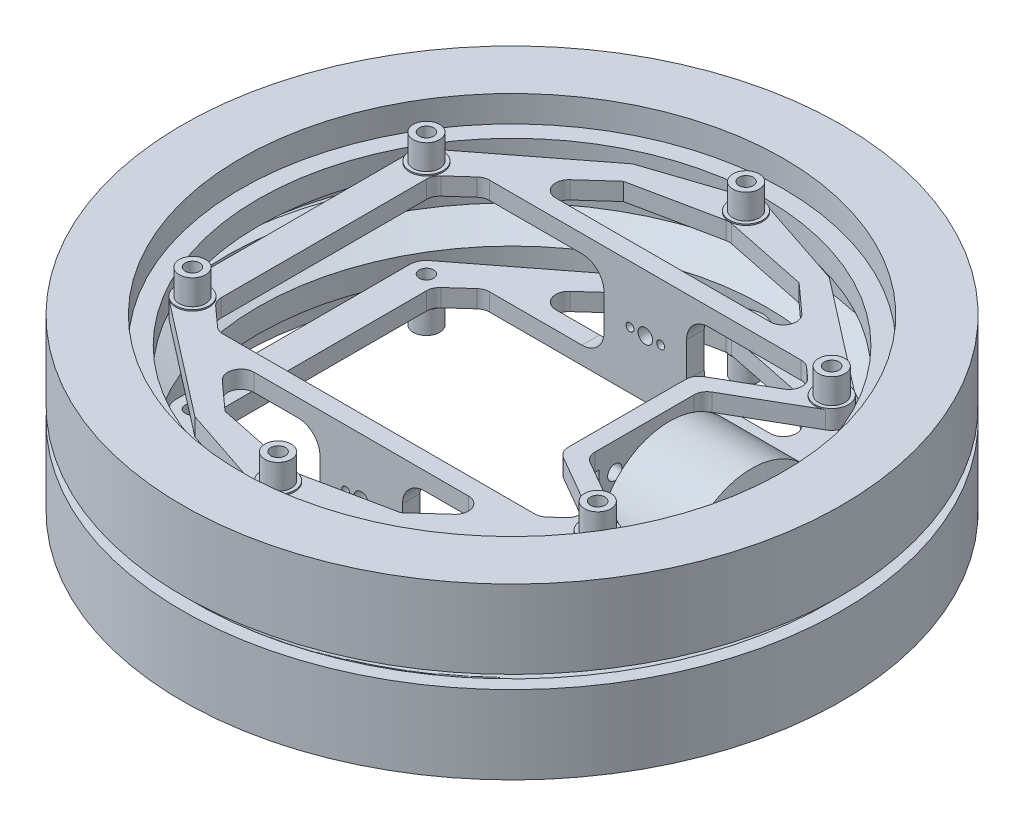
SolidWorks part; units mm, degrees
material "ABS"
ref_plane "Front Plane" through (0, 0, 0) normal (0, 0, 1) x (1, 0, 0)
ref_plane "Top Plane" through (0, 0, 0) normal (0, 1, 0) x (1, 0, 0)
ref_plane "Right Plane" through (0, 0, 0) normal (1, 0, 0) x (0, 0, -1)
other "Center of Mass"
ref_axis "Axis1" through (0, -45.4923, 0) along (0, 1, 0)
sketch "Sketch3" plane through (0, 0, 0) normal (0, 0, 1) x (1, 0, 0)
  line L0 (65, 1.5) -> (75, 1.5)
  line L1 (75, 1.5) -> (75, 19.3)
  line L2 (75, 19.3) -> (61.7495, 19.3)
  line L3 (0, 0) -> (85.6752, 0) construction
  line L4 (52.3451, 13.8) -> (57.3812, 3)
  line L5 (65, 1.5) -> (65, 4.5601)
  line L14 (35.8451, 16.3) -> (35.8451, 13.8)
  line L15 (35.8451, 13.8) -> (52.3451, 13.8)
  line L17 (54.4894, 16.3) -> (35.8451, 16.3)
  line L22 (0, -45.4923) -> (0, 86.3395) construction
  line L23 (57.3812, 3) -> (64.5, 3)
  line L24 (64.5, 3) -> (64.5, 7)
  line L25 (64.5, 7) -> (57.2495, 10.3809)
  line L26 (57.2495, 10.3809) -> (54.4894, 16.3)
  line L27 (65, 4.5601) -> (57.7495, 7.941)
  line L28 (57.7495, 7.941) -> (57.7495, 13.3)
  line L29 (57.7495, 13.3) -> (61.7495, 13.3)
  line L30 (61.7495, 13.3) -> (61.7495, 19.3)
  line L31 (53.2495, 19.3) -> (53.2495, 13.3) construction
  line L32 (44.7495, 19.3) -> (61.7495, 19.3) construction
  line L33 (44.7495, 19.3) -> (44.7495, 13.3) construction
  line L34 (44.7495, 13.3) -> (61.7495, 13.3) construction
  line L35 (61.7495, 19.3) -> (61.7495, 13.3) construction
  line L36 (50.2495, 19.3) -> (50.2495, 13.3) construction
  line L37 (56.2495, 19.3) -> (56.2495, 13.3) construction
  line L38 (75, -1.5) -> (75, -19.3)
  line L39 (65, -1.5) -> (75, -1.5)
  line L40 (65, -1.5) -> (65, -4.5601)
  line L41 (65, -4.5601) -> (57.7495, -7.941)
  line L42 (57.7495, -7.941) -> (57.7495, -13.3)
  line L43 (57.7495, -13.3) -> (61.7495, -13.3)
  line L44 (61.7495, -13.3) -> (61.7495, -19.3)
  line L45 (75, -19.3) -> (61.7495, -19.3)
  circle A0 centre (70, 0) radius 2.5
  point P32 (64.4892, 1.5)
  point P33 (56.9831, 0)
  point P34 (70, 1.5)
  point P35 (34.6232, 13.9)
  point P36 (49, 3.5657)
  point P45 (75.8697, 16.9)
  point P46 (75, 5.8131)
  dimension "D6" = 3
  dimension "D7" = 5
  dimension "D3" = 0.5
  dimension "D4" = 115
  dimension "D5" = 3
  dimension "D8" = 17
  dimension "D9" = 4
  dimension "D10" = 2.5
  dimension "D11" = 65
  dimension "D12" = 25
  dimension "D13" = 6
  dimension "D16" = 10
  dimension "D17" = 8
  dimension "D18" = 27.6
  dimension "D19" = 16.5
  dimension "D20" = 3
  dimension "D21" = 7
  dimension "D22" = 3
  dimension "D23" = 0.5
  dimension "D24" = 75
  dimension "D25" = 2
  dimension "D14" = 3
  dimension "D15" = 3
revolve "Revolve1" add sketch "Sketch3" angle 360 about axis through (0, -45.4923, 0) along (0, 1, 0) region at (68.168, 11.0369, 0) region at (67.7412, -10.8207, 0) region at (61.1248, 7.4705, 0)
revolve "Revolve2" add sketch "Sketch3<3>" angle 360 about L3 region at (61.1248, 7.4705, 0) region at (64.1841, 3.8966, 0)
sketch "Sketch3<3>" plane through (0, 0, 0) normal (0, 0, 1) x (1, 0, 0) same geometry as "Sketch3"
sketch "Sketch4" plane through (0, 0, 0) normal (0, 1, 0) x (1, 0, 0)
  line L0 (0, 0) -> (0, 53.2495) construction
  line L1 (0, 0) -> (46.1155, 26.6248) construction
  line L2 (0, 0) -> (46.1155, -26.6248) construction
  line L3 (0, 0) -> (0, -53.2495) construction
  line L4 (0, 0) -> (-46.1155, -26.6248) construction
  line L5 (0, 0) -> (-46.1155, 26.6248) construction
  line L6 (-1.2011, 56.8547) -> (-22.3876, 49.7965)
  line L7 (-48.4414, 29.6297) -> (-22.3876, 49.7965)
  line L8 (-49.9155, 26.6248) -> (-49.9155, -26.6248)
  line L9 (48.4414, 29.6297) -> (22.3876, 49.7965)
  line L10 (1.2011, 56.8547) -> (22.3876, 49.7965)
  line L11 (0, 0) -> (130.3481, 0) construction
  line L12 (48.0155, 23.3339) -> (30.1301, 13.0077)
  line L13 (30.1301, 13.0077) -> (30.1301, -13.0077)
  line L14 (48.0155, -23.3339) -> (30.1301, -13.0077)
  line L15 (35.8451, 13.8) -> (35.8451, -13.8) construction
  line L16 (48.4414, -29.6297) -> (22.3876, -49.7965)
  line L17 (-20, 45.3218) -> (20, 45.3218) construction
  line L18 (-20, 45.3218) -> (-20, 35.3218) construction
  line L19 (-20, 35.3218) -> (20, 35.3218) construction
  line L20 (20, 45.3218) -> (20, 35.3218) construction
  line L21 (1.2011, -56.8547) -> (22.3876, -49.7965)
  line L22 (-1.2011, -56.8547) -> (-22.3876, -49.7965)
  line L23 (-48.4414, -29.6297) -> (-22.3876, -49.7965)
  line L24 (-20, 45.3218) -> (-42.8246, 24.7248)
  line L25 (-20, 45.3218) -> (0, 49.4495)
  line L26 (0, 49.4495) -> (20, 45.3218)
  line L27 (20, 45.3218) -> (42.8246, 24.7248)
  line L28 (-32.1896, 34.3218) -> (32.1896, 34.3218)
  line L29 (-36.6222, 30.3218) -> (36.6222, 30.3218)
  line L30 (-42.8246, 24.7248) -> (-42.8246, -24.7248)
  line L31 (26.1301, -15.0862) -> (26.1301, 15.0862)
  line L32 (26.1301, 15.0862) -> (42.8246, 24.7248)
  line L33 (-32.1896, -34.3218) -> (32.1896, -34.3218)
  line L34 (-36.6222, -30.3218) -> (36.6222, -30.3218)
  line L35 (-20, -45.3218) -> (-42.8246, -24.7248)
  line L36 (0, -49.4495) -> (20, -45.3218)
  line L37 (-20, -45.3218) -> (0, -49.4495)
  line L38 (20, -45.3218) -> (42.8246, -24.7248)
  line L39 (26.1301, -15.0862) -> (42.8246, -24.7248)
  circle A1 centre (0, 53.2495) radius 3
  circle A3 centre (0, 53.2495) radius 3.8
  circle A4 centre (0, 53.2495) radius 1.65
  circle A5 centre (46.1155, 26.6248) radius 1.65
  circle A6 centre (46.1155, 26.6248) radius 3
  circle A7 centre (46.1155, 26.6248) radius 3.8
  circle A8 centre (46.1155, -26.6248) radius 1.65
  circle A9 centre (46.1155, -26.6248) radius 3
  circle A10 centre (46.1155, -26.6248) radius 3.8
  circle A11 centre (0, -53.2495) radius 1.65
  circle A12 centre (0, -53.2495) radius 3
  circle A13 centre (0, -53.2495) radius 3.8
  circle A14 centre (-46.1155, -26.6248) radius 1.65
  circle A15 centre (-46.1155, -26.6248) radius 3
  circle A16 centre (-46.1155, -26.6248) radius 3.8
  circle A17 centre (-46.1155, 26.6248) radius 1.65
  circle A18 centre (-46.1155, 26.6248) radius 3
  circle A19 centre (-46.1155, 26.6248) radius 3.8
  circle A20 centre (0, 53.2495) radius 8.5
  circle A21 centre (0, 0) radius 61.7495 construction
  point P32 (0, 0)
  point P44 (0, 45.3218)
  point P48 (30.1301, 0)
  point P63 (-49.9155, 0)
  point P78 (-42.8246, 0)
  point P83 (26.1301, 0)
  dimension "D1" = 6
  dimension "D2" = 17
  dimension "D4" = 0.8
  dimension "D5" = 3.3
  dimension "D13" = 1
  dimension "D7" = 5.715
  dimension "D8" = 10
  dimension "D9" = 40
  dimension "D10" = 5
  dimension "D11" = 5
  dimension "D12" = 4.1278
  dimension "D14" = 4
  dimension "D15" = 4
  dimension "D6" = 6
extrude "Boss-Extrude1" add sketch "Sketch4" along normal blind 4 from offset 9 separate body contours A19 L24 L25 A3 L6 L7 | A7 L9 L10 A3 L26 L27 | A3 A1 | A1 A4 | A7 A6 | A6 A5 | A10 L14 L13 L12 A7 L32 L31 L39 | A10 A9 | A9 A8 | A13 L21 L16 A10 L38 L36 | A12 A11 | A16 L23 L22 A13 L37 L35 | A13 A12 | A16 A15 | A15 A14 | A19 L8 A16 L30 | A19 A18 | A18 A17 | L24 L29 L27 L28 | L33 L38 L34 L35 | L26 A20 L10 A3 | L6 A20 L25 A3 region at (-5.4103, 0, -51.8523) region at (0, 0, -56.9421) region at (-27.4512, 0, -41.1917) region at (5.4103, 0, -51.8523) region at (27.4512, 0, -41.1917) region at (-44.4893, 0, -29.9399) region at (-46.3899, 0, 0) region at (49.4306, 0, -28.2509) region at (0, 0, -32.2788) region at (-47.0711, 0, 23.0581) region at (44.992, 0, -22.4319) region at (-24.7667, 0, 42.4901) region at (0, 0, 32.2788) region at (24.7667, 0, 42.4901) region at (-3.6449, 0, 52.6584) region at (45.1598, 0, 23.0581) region at (-2.9151, 0, -53.2495) region at (43.2003, 0, -26.6248) region at (43.2003, 0, 26.6248) region at (-2.9151, 0, 53.2495) region at (-49.0306, 0, 26.6248) region at (-49.0306, 0, -26.6248)
extrude "Boss-Extrude5" add sketch "Sketch4<3>" along normal up to surface (13.3 mm away) from surface contours A3 A1 | A1 A4 | A6 A5 | A7 A6 | A9 A8 | A10 A9 | A13 A12 | A12 A11 | A16 A15 | A15 A14 | A19 A18 | A18 A17 region at (0, 0, -56.9421) region at (-44.4893, 0, -29.9399) region at (49.4306, 0, -28.2509) region at (-47.0711, 0, 23.0581) region at (-3.6449, 0, 52.6584) region at (45.1598, 0, 23.0581) region at (-2.9151, 0, -53.2495) region at (43.2003, 0, -26.6248) region at (43.2003, 0, 26.6248) region at (-2.9151, 0, 53.2495) region at (-49.0306, 0, 26.6248) region at (-49.0306, 0, -26.6248) up to face at (0, 13.3, -61.7495) starting at face at (3.2844, 9, 0)
sketch "Sketch4<3>" plane through (0, 0, 0) normal (0, 1, 0) x (1, 0, 0) same geometry as "Sketch4"
extrude "Boss-Extrude6" add sketch "Sketch4<4>" along normal blind 6 from surface contours A18 A17 | A15 A14 | A12 A11 | A9 A8 | A6 A5 | A1 A4 region at (-2.9151, 0, -53.2495) region at (43.2003, 0, -26.6248) region at (43.2003, 0, 26.6248) region at (-2.9151, 0, 53.2495) region at (-49.0306, 0, 26.6248) region at (-49.0306, 0, -26.6248) starting at face at (0, 13, 40.2774)
sketch "Sketch4<4>" plane through (0, 0, 0) normal (0, 1, 0) x (1, 0, 0) same geometry as "Sketch4"
fillet "Fillet2" radius 3 18 edges at (30.1301, 11, -13.0077) (30.1301, 11, 13.0077) (32.1896, 11, -34.3218) (-32.1896, 11, -34.3218) (0, 11, -49.4495) (32.1896, 11, 34.3218) (-32.1896, 11, 34.3218) (0, 11, 49.4495) (-36.6222, 11, -30.3218) (36.6222, 11, -30.3218) (42.8246, 11, -24.7248) (26.1301, 11, -15.0862) (26.1301, 11, 15.0862) (42.8246, 11, 24.7248) (36.6222, 11, 30.3218) (-42.8246, 11, 24.7248) (-42.8246, 11, -24.7248) (-36.6222, 11, 30.3218)
mirror "Mirror2" about plane through (0, 0, 0) normal (0, 1, 0) of bodies 113 105
sketch "Sketch7" plane through (26.1301, 0, 0) normal (-1, 0, 0) x (0, 0, 1)
  line L0 (13.3542, -9) -> (-13.3542, -9) construction
  line L1 (-10.3852, -9) -> (10.3852, -9)
  line L2 (-10.3852, -9) -> (-10.3852, 9)
  line L3 (-10.3852, 9) -> (10.3852, 9)
  line L4 (10.3852, -9) -> (10.3852, 9)
  line L5 (13.3542, 9) -> (-13.3542, 9) construction
  line L6 (-6.7352, -6.7352) -> (6.7352, 6.7352) construction
  line L7 (-5.5508, 5.5508) -> (5.5508, -5.5508) construction
  circle A0 centre (6.7352, 6.7352) radius 1.65
  circle A1 centre (-5.5508, 5.5508) radius 1.65
  circle A2 centre (-6.7352, -6.7352) radius 1.65
  circle A3 centre (5.5508, -5.5508) radius 1.65
  point P9 (0, -9)
  point P18 (-4.658, 4.658)
  point P19 (4.0383, -4.0383)
  dimension "D3" = 3.3
  dimension "D6" = 2
  dimension "D1" = 90
  dimension "D2" = 45
  dimension "D4" = 19.05
  dimension "D5" = 15.7
extrude "Boss-Extrude7" add sketch "Sketch7" against normal up to surface (4 mm away) up to face at (30.1301, 11, 0)
sketch "Sketch8" plane through (0, 0, -30.3218) normal (0, 0, 1) x (1, 0, 0)
  line L0 (1.2011, 9) -> (22.3876, 9) construction
  line L1 (-9.4, -9) -> (9.4, -9)
  line L2 (-9.4, -9) -> (-9.4, 9)
  line L3 (-9.4, 9) -> (9.4, 9)
  line L4 (9.4, -9) -> (9.4, 9)
  line L5 (-9.4, -9) -> (9.4, 9) construction
  line L6 (-9.4, 9) -> (9.4, -9) construction
  line L7 (-3.5, 0) -> (3.5, 0) construction
  circle A0 centre (0, 0) radius 1.65
  circle A1 centre (-3.5, 0) radius 0.9
  circle A2 centre (3.5, 0) radius 0.9
  point P0 (0, 0)
  point P14 (6.2509, 0)
  dimension "D1" = 1.8
  dimension "D2" = 7
  dimension "D3" = 3.3
  dimension "D4" = 5
extrude "Boss-Extrude8" add sketch "Sketch8" against normal blind 4
mirror "Mirror4" about plane through (0, 0, 0) normal (0, 0, 1) of "Boss-Extrude8"
fillet "Fillet1" radius 5 8 edges at (-9.4, -9, 32.3218) (-9.4, 9, 32.3218) (-9.4, 9, -32.3218) (-9.4, -9, -32.3218) (9.4, -9, 32.3218) (9.4, 9, 32.3218) (9.4, 9, -32.3218) (9.4, -9, -32.3218)
